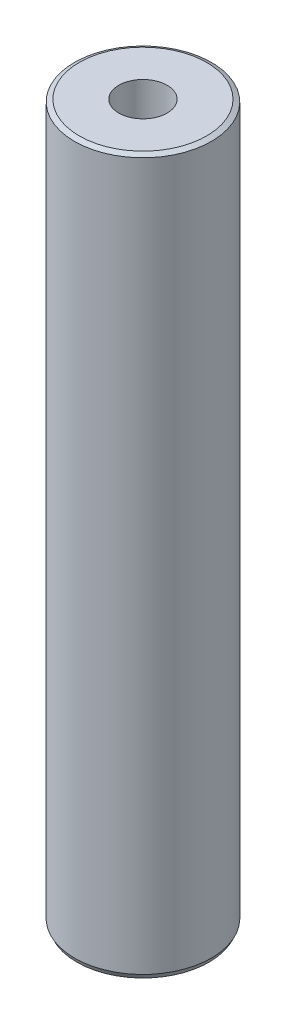
SolidWorks part; units mm, degrees
ref_plane "Front Plane" through (0, 0, 0) normal (0, 0, 1) x (1, 0, 0)
ref_plane "Top Plane" through (0, 0, 0) normal (0, 1, 0) x (1, 0, 0)
ref_plane "Right Plane" through (0, 0, 0) normal (1, 0, 0) x (0, 0, -1)
sketch "Sketch1" plane through (0, 0, 0) normal (0, 1, 0) x (1, 0, 0)
  circle A0 centre (0, 0) radius 57.5
  dimension "SHAFT_OD" = 115
extrude "Boss-Extrude1" add sketch "Sketch1" along normal blind 600
sketch "Sketch2" plane through (0, 0, 0) normal (0, 1, 0) x (1, 0, 0)
  circle A0 centre (0, 0) radius 20.2998
  dimension "BORE_D" = 40.5997
extrude "Cut-Extrude1" cut sketch "Sketch2" along normal through all
chamfer "Chamfer1" distance 1.9845 angle 63.605 2 edges at (0, 600, 57.5) (0, 0, 57.5) first distance on face at (0, 600, 57.5) first distance on face at (0, 0, 20.2998)
